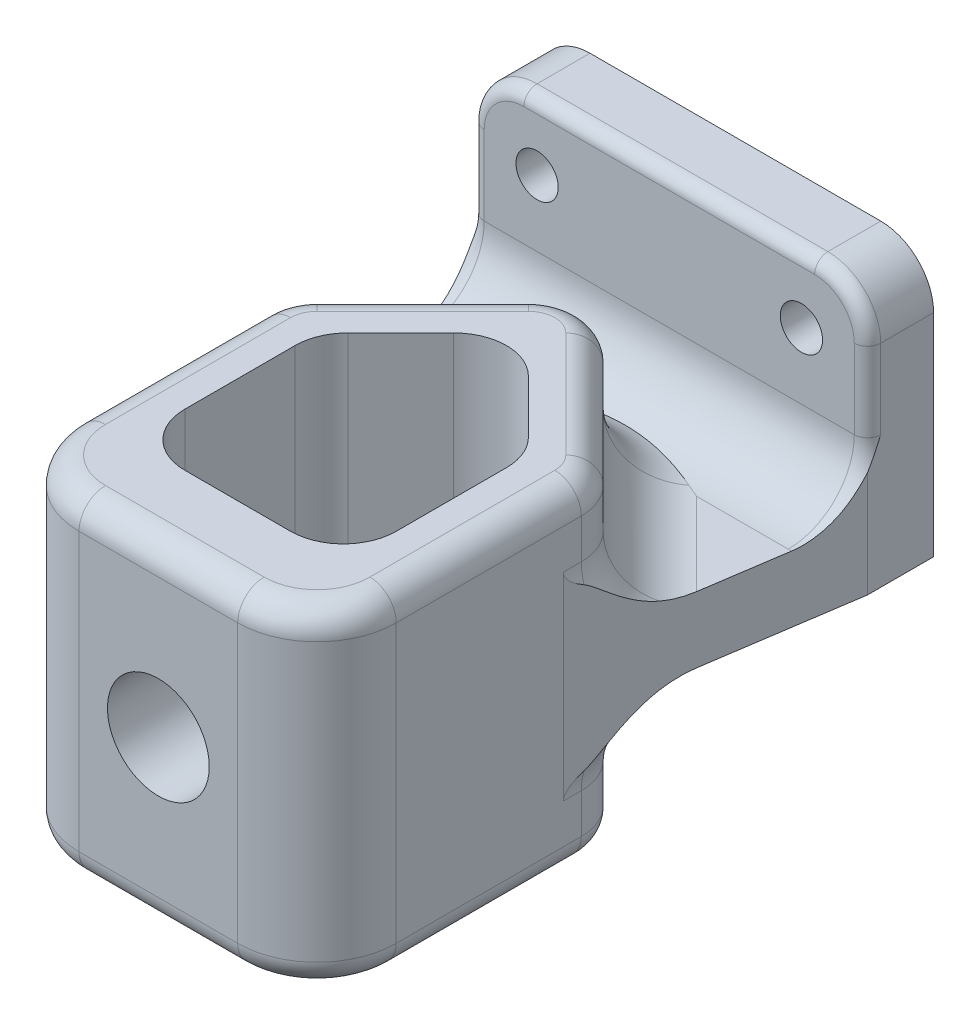
SolidWorks part; units mm, degrees
material "ABS"
ref_plane "前视基准面" through (0, 0, 0) normal (0, 0, 1) x (1, 0, 0)
ref_plane "上视基准面" through (0, 0, 0) normal (0, 1, 0) x (1, 0, 0)
ref_plane "右视基准面" through (0, 0, 0) normal (1, 0, 0) x (0, 0, -1)
other "Configuration Table"
sketch "草图1" plane through (0, 0, 0) normal (0, 0, 1) x (1, 0, 0)
  line L0 (0, 7.5) -> (0, -7.5) construction
  line L1 (-15, -7.5) -> (15, -7.5)
  line L2 (-15, -7.5) -> (-15, 7.5)
  line L3 (-15, 7.5) -> (15, 7.5)
  line L4 (15, -7.5) -> (15, 7.5)
  line L5 (-15, -7.5) -> (15, 7.5) construction
  line L6 (-15, 7.5) -> (15, -7.5) construction
  circle A2 centre (-10, 2.5) radius 1.6
  circle A3 centre (10, 2.5) radius 1.6
  point P0 (0, 0)
  dimension "D1" = 20
  dimension "D4" = 5
  dimension "D2" = 30
  dimension "D3" = 15
extrude "凸台-拉伸1" add sketch "草图1" along normal blind 5
sketch "草图3" plane through (0, -7.5, 0) normal (0, -1, 0) x (1, 0, 0)
  line L0 (15, 5) -> (15, 0) construction
  line L1 (-15, 0) -> (15, 0)
  line L2 (-15, 0) -> (-15, 25) construction
  line L3 (-15, 25) -> (0, 25) construction
  line L4 (15, 0) -> (15, 25) construction
  line L5 (0, 25) -> (0, 0) construction
  line L6 (0, 25) -> (15, 25) construction
  line L7 (12, 25) -> (-12, 25)
  line L8 (15, 0) -> (15, 5)
  line L9 (15, 5) -> (12, 25)
  line L10 (-15, 0) -> (-15, 5)
  line L11 (-15, 5) -> (-12, 25)
  point P12 (0, 25)
  dimension "D1" = 25
  dimension "D2" = 24
extrude "凸台-拉伸2" add sketch "草图3" along normal blind 5
sketch "草图4" plane through (0, -7.5, 0) normal (0, 1, 0) x (1, 0, 0)
  line L0 (0, -1031.6825) -> (0, 48968.3175) construction
  line L2 (8, -37.6569) -> (-8, -37.6569)
  line L3 (0, -15.6569) -> (8, -23.6569)
  line L4 (0, -15.6569) -> (-8, -23.6569)
  line L5 (0, -10) -> (12, -22)
  line L7 (0, -10) -> (-12, -22)
  line L12 (15, -5) -> (-15, -5) construction
  line L13 (8, -23.6569) -> (8, -37.6569)
  line L14 (-8, -37.6569) -> (-8, -23.6569)
  line L15 (-12, -22) -> (-12, -43.6569)
  line L16 (-12, -43.6569) -> (12, -43.6569)
  line L17 (12, -43.6569) -> (12, -22)
  circle A0 centre (0, -26.9706) radius 8 construction
  circle A1 centre (0, -22.7279) radius 5 construction
  dimension "D9" = 16
  dimension "D10" = 10
  dimension "D1" = 45
  dimension "D2" = 45
  dimension "D3" = 24
  dimension "D4" = 4
  dimension "D5" = 5
  dimension "D6" = 4
  dimension "D7" = 4
  dimension "D8" = 6
  dimension "D11" = 14
extrude "凸台-拉伸3" add sketch "草图4" against normal offset from surface (25 mm away) 10 from offset 10 up to face at (0, -12.5, 10) offset beyond the face yes
sketch "草图5" plane through (0, 0, 43.6569) normal (0, 0, 1) x (1, 0, 0)
  line L0 (0, 2.5) -> (0, -22.5) construction
  line L1 (-12, 2.5) -> (12, 2.5) construction
  line L2 (12, -22.5) -> (-12, -22.5) construction
  circle A0 centre (0, -10) radius 3.85
  dimension "D1" = 7.7
extrude "切除-拉伸1" cut sketch "草图5" against normal up to next
sketch "草图7" plane through (0, 2.5, 0) normal (0, 1, 0) x (1, 0, 0)
  line L3 (-8, -23.6569) -> (-8, -25)
  line L5 (0, -15.6569) -> (-8, -23.6569)
  line L8 (-8, -23.6569) -> (-8, -25)
  line L9 (8, -23.6569) -> (0, -15.6569)
  line L10 (0, -15.6569) -> (-8, -23.6569)
  line L14 (8, -23.6569) -> (0, -15.6569)
  line L15 (-8, -25) -> (8, -25)
  line L17 (8, -25) -> (8, -23.6569)
  line L18 (8, -25) -> (8, -23.6569)
  line L19 (-8, -25) -> (8, -25)
  dimension "D1" = 0
extrude "切除-拉伸3" cut sketch "草图7" against normal through all both and the other way through all
fillet "圆角1" radius 4 11 edges at (-12, -2.5, 22) (12, -2.5, 22) (0, -2.5, 10) (8, -10, 37.6569) (-8, -10, 37.6569) (8, -10, 23.6569) (-8, -10, 23.6569) (0, -10, 15.6569) (-12, -17.5, 22) (12, -17.5, 22) (0, -17.5, 10)
fillet "圆角2" radius 6 2 edges at (12, -10, 43.6569) (-12, -10, 43.6569)
fillet "圆角3" radius 2 20 edges at (0, 2.5, 11.6569) (6.8284, 2.5, 16.8284) (11.6955, 2.5, 22.1261) (12, 2.5, 30.6569) (10.2426, 2.5, 41.8995) (0, 2.5, 43.6569) (-10.2426, 2.5, 41.8995) (-12, 2.5, 30.6569) (-11.6955, 2.5, 22.1261) (-6.8284, 2.5, 16.8284) (-10.2426, -22.5, 41.8995) (0, -22.5, 43.6569) (10.2426, -22.5, 41.8995) (12, -22.5, 30.6569) (11.6955, -22.5, 22.1261) (6.8284, -22.5, 16.8284) (0, -22.5, 11.6569) (-6.8284, -22.5, 16.8284) (-11.6955, -22.5, 22.1261) (-12, -22.5, 30.6569)
fillet "圆角4" radius 4 2 edges at (15, 7.5, 2.5) (-15, 7.5, 2.5)
fillet "圆角9" radius 1 5 edges at (15, -2, 5) (13.8284, 6.3284, 5) (0, 7.5, 5) (-13.8284, 6.3284, 5) (-15, -2, 5) tangent propagation no
fillet "圆角10" radius 5 13 edges at (-12, -7.5, 24.3284) (12, -7.5, 24.3284) (6.8284, -7.5, 16.8284) (0, -7.5, 11.6569) (-12, -12.5, 24.3284) (12, -12.5, 24.3284) (6.8284, -12.5, 16.8284) (0, -12.5, 11.6569) (-14.7071, -7.5, 4.7071) (14.7071, -7.5, 4.7071) (-6.8284, -7.5, 16.8284) (-6.8284, -12.5, 16.8284) (0, -7.5, 5)
